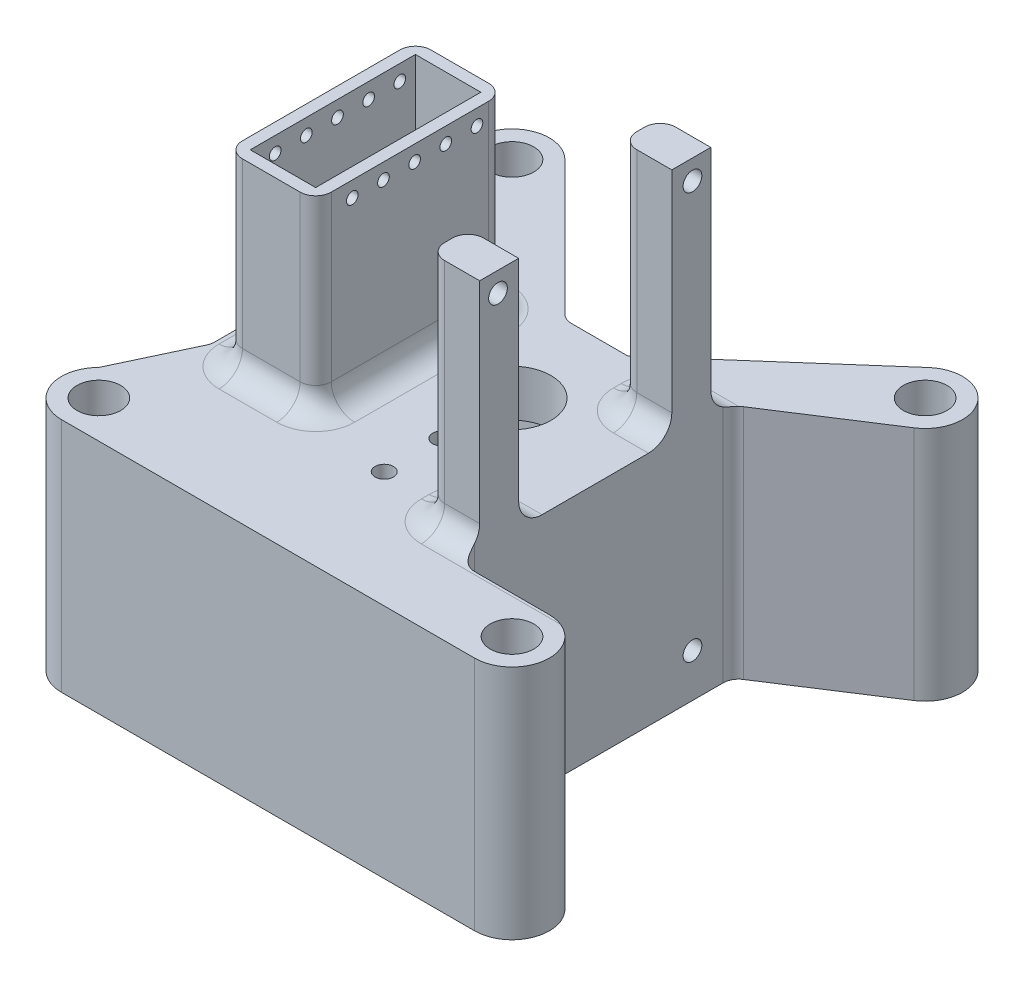
SolidWorks part; units mm, degrees
ref_plane "Front Plane" through (0, 0, 0) normal (0, 0, 1) x (1, 0, 0)
ref_plane "Top Plane" through (0, 0, 0) normal (0, 1, 0) x (1, 0, 0)
ref_plane "Right Plane" through (0, 0, 0) normal (1, 0, 0) x (0, 0, -1)
sketch "Sketch3" plane through (0, 0, 0) normal (0, 1, 0) x (1, 0, 0)
  line L0 (-33.676, -39.772) -> (33.676, -39.772)
  line L1 (-33.676, -33.676) -> (33.676, -33.676) construction
  line L2 (-33.676, -33.676) -> (-33.676, 33.676) construction
  line L3 (-33.676, 33.676) -> (33.676, 33.676) construction
  line L4 (33.676, -33.676) -> (33.676, 33.676) construction
  line L5 (-33.676, -33.676) -> (33.676, 33.676) construction
  line L6 (-33.676, 33.676) -> (33.676, -33.676) construction
  line L7 (10.033, -30.099) -> (-10.033, -30.099)
  line L8 (10.033, -30.099) -> (10.033, 10.033)
  line L9 (10.033, 10.033) -> (3.556, 10.033)
  line L10 (-10.033, -30.099) -> (-10.033, 10.033)
  line L11 (10.033, -30.099) -> (-10.033, 10.033) construction
  line L12 (10.033, 10.033) -> (-10.033, -30.099) construction
  line L13 (33.676, -27.58) -> (18.923, -27.58)
  line L14 (-3.556, 15.367) -> (3.556, 15.367) construction
  line L15 (-3.556, 15.367) -> (-3.556, 10.033)
  line L16 (0, 10.033) -> (3.556, 10.033) construction
  line L17 (3.556, 15.367) -> (3.556, 10.033)
  line L18 (-3.556, 15.367) -> (3.556, 10.033) construction
  line L19 (-3.556, 10.033) -> (3.556, 15.367) construction
  line L20 (-25.781, 10.033) -> (-15.113, 10.033) construction
  line L21 (-25.781, 10.033) -> (-25.781, -16.891) construction
  line L22 (-25.781, -16.891) -> (-15.113, -16.891) construction
  line L23 (-15.113, 10.033) -> (-15.113, -16.891) construction
  line L24 (-25.781, 10.033) -> (-15.113, -16.891) construction
  line L25 (-25.781, -16.891) -> (-15.113, 10.033) construction
  line L26 (18.923, -27.58) -> (18.923, 16.87)
  line L27 (36.9874, 28.5578) -> (18.923, 16.87)
  line L28 (29.6563, 38.259) -> (3.556, 15.367)
  line L31 (0, 10.033) -> (-3.556, 10.033) construction
  line L32 (-29.3669, 37.9879) -> (-6.731, 15.367)
  line L33 (-6.731, 15.367) -> (-3.556, 15.367)
  line L34 (-3.556, 10.033) -> (-10.033, 10.033)
  line L35 (-3.556, 10.033) -> (0, 10.033) construction
  line L36 (3.556, 10.033) -> (0, 10.033) construction
  line L37 (-32.131, -16.891) -> (-32.131, 10.033)
  line L38 (34.003, -24.1637) -> (18.923, -24.1637) construction
  line L39 (34.003, -24.1637) -> (34.003, 13.4537) construction
  line L40 (34.003, 13.4537) -> (18.923, 13.4537) construction
  line L41 (18.923, -24.1637) -> (18.923, 13.4537) construction
  line L42 (34.003, -24.1637) -> (18.923, 13.4537) construction
  line L43 (34.003, 13.4537) -> (18.923, -24.1637) construction
  line L44 (-32.131, 10.033) -> (-39.4519, 31.7268)
  line L45 (-32.131, -16.891) -> (-37.9865, -29.3654)
  circle A0 centre (-33.676, 33.676) radius 3.556
  circle A1 centre (33.676, 33.676) radius 3.556
  circle A2 centre (33.676, -33.676) radius 3.556
  circle A3 centre (-33.676, -33.676) radius 3.556
  circle A4 centre (0, 0) radius 6.35 construction
  circle A5 centre (0, 0) radius 10.033 construction
  circle A6 centre (0, 0) radius 63.373 construction
  arc A7 (33.676, -39.772) -> (33.676, -27.58) centre (33.676, -33.676) ccw
  arc A8 (-39.772, -33.676) -> (-33.676, -39.772) centre (-33.676, -33.676) ccw
  arc A9 (-29.3669, 37.9879) -> (-39.772, 33.676) centre (-33.676, 33.676) ccw
  arc A10 (36.9874, 28.5578) -> (29.6563, 38.259) centre (33.676, 33.676) ccw
  arc A11 (27.58, 33.676) -> (29.3654, 29.3654) centre (33.676, 33.676) ccw construction
  arc A12 (29.6563, 38.259) -> (27.58, 33.676) centre (33.676, 33.676) ccw construction
  arc A13 (29.3654, 29.3654) -> (33.676, 27.58) centre (33.676, 33.676) ccw construction
  arc A14 (33.676, 27.58) -> (36.9874, 28.5578) centre (33.676, 33.676) ccw construction
  arc A15 (-27.58, 33.676) -> (-29.3669, 37.9879) centre (-33.676, 33.676) ccw construction
  arc A16 (-29.3654, 29.3654) -> (-27.58, 33.676) centre (-33.676, 33.676) ccw construction
  arc A17 (-33.676, 27.58) -> (-29.3654, 29.3654) centre (-33.676, 33.676) ccw construction
  arc A18 (-39.772, 33.676) -> (-39.4519, 31.7268) centre (-33.676, 33.676) ccw
  arc A19 (-37.9865, -29.3654) -> (-39.772, -33.676) centre (-33.676, -33.676) ccw
  arc A20 (-29.3654, -29.3654) -> (-33.676, -27.58) centre (-33.676, -33.676) ccw construction
  arc A21 (-27.58, -33.676) -> (-29.3654, -29.3654) centre (-33.676, -33.676) ccw construction
  arc A22 (-33.676, -39.772) -> (-27.58, -33.676) centre (-33.676, -33.676) ccw construction
  arc A23 (33.676, -27.58) -> (29.3654, -29.3654) centre (33.676, -33.676) ccw construction
  arc A24 (29.3654, -29.3654) -> (27.58, -33.676) centre (33.676, -33.676) ccw construction
  arc A25 (27.58, -33.676) -> (33.676, -39.772) centre (33.676, -33.676) ccw construction
  arc A26 (-39.4519, 31.7268) -> (-33.676, 27.58) centre (-33.676, 33.676) ccw construction
  arc A27 (-33.676, -27.58) -> (-37.9865, -29.3654) centre (-33.676, -33.676) ccw construction
  point P0 (0, 0)
  point P10 (0, -10.033)
  point P25 (0, 12.7)
  point P30 (3.556, 12.7)
  point P32 (-20.447, -3.429)
  point P53 (18.923, -5.355)
  point P55 (26.463, -5.355)
  point P64 (-32.131, -3.429)
  dimension "D2" = 7.112
  dimension "D5" = 12.7
  dimension "D6" = 126.746
  dimension "D1" = 95.25
  dimension "D3" = 40.132
  dimension "D4" = 20.066
  dimension "D7" = 2.54
  dimension "D8" = 5.334
  dimension "D9" = 7.112
  dimension "D10" = 10.668
  dimension "D11" = 26.924
  dimension "D12" = 5.08
  dimension "D13" = 8.89
  dimension "D14" = 171.65
  dimension "D15" = 352.506
  dimension "D16" = 44.45
  dimension "D17" = 37.6174
  dimension "D18" = 3.175
  dimension "D19" = 30.16
  dimension "D21" = 6.35
  dimension "D20" = 67.3519
extrude "Boss-Extrude1" add sketch "Sketch3" along normal blind 21.463
sketch "Sketch4" plane through (0, 21.463, 0) normal (0, 1, 0) x (1, 0, 0)
  line L0 (-3.556, 15.367) -> (3.556, 15.367) construction
  line L1 (-3.556, 10.033) -> (3.556, 10.033) construction
  line L2 (3.556, 15.367) -> (-3.556, 15.367)
  line L3 (-3.556, 10.033) -> (3.556, 10.033)
  line L16 (-10.033, 10.033) -> (-3.556, 10.033)
  line L17 (-3.556, 10.033) -> (-3.556, 15.367)
  line L18 (-3.556, 15.367) -> (-6.731, 15.367)
  line L19 (-6.731, 15.367) -> (-29.3669, 37.9879)
  line L20 (-39.4519, 31.7268) -> (-32.131, 10.033)
  line L21 (-33.676, -39.772) -> (33.676, -39.772)
  line L22 (33.676, -27.58) -> (18.923, -27.58)
  line L23 (18.923, -27.58) -> (18.923, 16.87)
  line L24 (18.923, 16.87) -> (36.9874, 28.5578)
  line L25 (29.6563, 38.259) -> (3.556, 15.367)
  line L27 (3.556, 15.367) -> (3.556, 10.033)
  line L28 (3.556, 10.033) -> (10.033, 10.033)
  line L29 (10.033, 10.033) -> (10.033, -30.099)
  line L30 (10.033, -30.099) -> (-10.033, -30.099)
  line L31 (-10.033, -30.099) -> (-10.033, 10.033)
  line L32 (-10.033, 10.033) -> (-3.556, 10.033)
  line L33 (-3.556, 10.033) -> (-3.556, 15.367) construction
  line L34 (-3.556, 15.367) -> (-6.731, 15.367)
  line L35 (-6.731, 15.367) -> (-29.3669, 37.9879)
  line L37 (-33.676, -39.772) -> (33.676, -39.772)
  line L38 (33.676, -27.58) -> (18.923, -27.58)
  line L39 (18.923, -27.58) -> (18.923, 16.87)
  line L40 (18.923, 16.87) -> (36.9874, 28.5578)
  line L41 (29.6563, 38.259) -> (3.556, 15.367)
  line L43 (3.556, 15.367) -> (3.556, 10.033) construction
  line L44 (3.556, 10.033) -> (10.033, 10.033)
  line L45 (10.033, 10.033) -> (10.033, -30.099)
  line L46 (10.033, -30.099) -> (-10.033, -30.099)
  line L47 (-10.033, -30.099) -> (-10.033, 10.033)
  line L52 (-39.4519, 31.7268) -> (-32.131, 10.033)
  line L53 (-32.131, 10.033) -> (-32.131, -16.891)
  line L54 (-32.131, 10.033) -> (-32.131, -16.891)
  line L55 (-32.131, -16.891) -> (-37.9865, -29.3654)
  line L56 (-32.131, -16.891) -> (-37.9865, -29.3654)
  circle A3 centre (33.676, -33.676) radius 3.556 construction
  arc A4 (-29.3669, 37.9879) -> (-39.4519, 31.7268) centre (-33.676, 33.676) ccw
  arc A5 (-37.9865, -29.3654) -> (-33.676, -39.772) centre (-33.676, -33.676) ccw
  arc A6 (33.676, -39.772) -> (33.676, -27.58) centre (33.676, -33.676) ccw
  arc A7 (36.9874, 28.5578) -> (29.6563, 38.259) centre (33.676, 33.676) ccw
  arc A8 (-29.3669, 37.9879) -> (-39.4519, 31.7268) centre (-33.676, 33.676) ccw
  arc A9 (-37.9865, -29.3654) -> (-33.676, -39.772) centre (-33.676, -33.676) ccw
  arc A10 (33.676, -39.772) -> (33.676, -27.58) centre (33.676, -33.676) ccw
  arc A11 (36.9874, 28.5578) -> (29.6563, 38.259) centre (33.676, 33.676) ccw
  circle A12 centre (33.676, -33.676) radius 3.556
  circle A13 centre (33.676, 33.676) radius 3.556 construction
  circle A14 centre (33.676, 33.676) radius 3.556
  circle A15 centre (-33.676, 33.676) radius 3.556 construction
  circle A16 centre (-33.676, 33.676) radius 3.556
  circle A17 centre (-33.676, -33.676) radius 3.556 construction
  circle A18 centre (-33.676, -33.676) radius 3.556
  dimension "D1" = 0
extrude "Boss-Extrude2" add sketch "Sketch4" along normal blind 7.366
sketch "Sketch5" plane through (0, 28.829, 0) normal (0, 1, 0) x (1, 0, 0)
  line L8 (3.556, 15.367) -> (-6.731, 15.367)
  line L9 (-6.731, 15.367) -> (-29.3669, 37.9879)
  line L10 (-39.4519, 31.7268) -> (-32.131, 10.033)
  line L11 (-33.676, -39.772) -> (33.676, -39.772)
  line L12 (33.676, -27.58) -> (18.923, -27.58)
  line L13 (18.923, -27.58) -> (18.923, 16.87)
  line L14 (18.923, 16.87) -> (36.9874, 28.5578)
  line L15 (29.6563, 38.259) -> (3.556, 15.367)
  line L16 (3.556, 15.367) -> (-6.731, 15.367)
  line L17 (-6.731, 15.367) -> (-29.3669, 37.9879)
  line L19 (-33.676, -39.772) -> (33.676, -39.772)
  line L20 (33.676, -27.58) -> (18.923, -27.58)
  line L21 (18.923, -27.58) -> (18.923, 16.87)
  line L22 (18.923, 16.87) -> (36.9874, 28.5578)
  line L23 (29.6563, 38.259) -> (3.556, 15.367)
  line L26 (-39.4519, 31.7268) -> (-32.131, 10.033)
  line L27 (-32.131, 10.033) -> (-32.131, -16.891)
  line L28 (-32.131, 10.033) -> (-32.131, -16.891)
  line L29 (-32.131, -16.891) -> (-37.9865, -29.3654)
  line L30 (-32.131, -16.891) -> (-37.9865, -29.3654)
  circle A0 centre (0, 0) radius 6.35 construction
  circle A1 centre (33.676, 33.676) radius 3.556
  circle A2 centre (33.676, 33.676) radius 3.556
  circle A3 centre (-33.676, 33.676) radius 3.556
  circle A4 centre (-33.676, 33.676) radius 3.556
  circle A5 centre (-33.676, -33.676) radius 3.556
  circle A6 centre (-33.676, -33.676) radius 3.556
  circle A7 centre (33.676, -33.676) radius 3.556
  circle A8 centre (33.676, -33.676) radius 3.556
  circle A9 centre (0, 0) radius 6.35
  arc A12 (-29.3669, 37.9879) -> (-39.4519, 31.7268) centre (-33.676, 33.676) ccw
  arc A13 (-37.9865, -29.3654) -> (-33.676, -39.772) centre (-33.676, -33.676) ccw
  arc A14 (33.676, -39.772) -> (33.676, -27.58) centre (33.676, -33.676) ccw
  arc A15 (36.9874, 28.5578) -> (29.6563, 38.259) centre (33.676, 33.676) ccw
  arc A16 (-29.3669, 37.9879) -> (-39.4519, 31.7268) centre (-33.676, 33.676) ccw
  arc A17 (-37.9865, -29.3654) -> (-33.676, -39.772) centre (-33.676, -33.676) ccw
  arc A18 (33.676, -39.772) -> (33.676, -27.58) centre (33.676, -33.676) ccw
  arc A19 (36.9874, 28.5578) -> (29.6563, 38.259) centre (33.676, 33.676) ccw
  dimension "D1" = 0
  dimension "D2" = 0
  dimension "D3" = 0
  dimension "D4" = 0
  dimension "D5" = 0
extrude "Boss-Extrude3" add sketch "Sketch5" along normal blind 7.62
sketch "Sketch6" plane through (0, 36.449, 0) normal (0, 1, 0) x (1, 0, 0)
  line L0 (-25.781, 10.033) -> (-25.781, -16.891) construction
  line L1 (-25.781, -16.891) -> (-15.113, -16.891) construction
  line L2 (-15.113, 10.033) -> (-15.113, -16.891) construction
  line L3 (-25.781, 10.033) -> (-15.113, 10.033) construction
  line L4 (-25.781, 10.033) -> (-25.781, -16.891) construction
  line L5 (-25.781, -16.891) -> (-15.113, -16.891) construction
  line L6 (-15.113, 10.033) -> (-15.113, -16.891) construction
  line L7 (-25.781, 10.033) -> (-15.113, 10.033) construction
  line L9 (-13.208, 11.938) -> (-27.686, 11.938)
  line L10 (-13.208, 11.938) -> (-13.208, -18.796)
  line L11 (-13.208, -18.796) -> (-27.686, -18.796)
  line L12 (-27.686, 11.938) -> (-27.686, -18.796)
  line L13 (-13.208, 11.938) -> (-27.686, -18.796) construction
  line L14 (-13.208, -18.796) -> (-27.686, 11.938) construction
  point P4 (-20.447, -3.429)
  point P11 (-20.447, -16.891)
  dimension "D1" = 1.905
  dimension "D2" = 1.905
extrude "Boss-Extrude4" add sketch "Sketch6" along normal blind 30.59
sketch "Sketch7" plane through (0, 67.039, 0) normal (0, 1, 0) x (1, 0, 0)
  line L0 (-25.781, 10.033) -> (-25.781, -16.891) construction
  line L1 (-25.781, -16.891) -> (-15.113, -16.891) construction
  line L2 (-15.113, 10.033) -> (-15.113, -16.891) construction
  line L3 (-25.781, 10.033) -> (-15.113, 10.033) construction
  line L4 (-25.781, 10.033) -> (-25.781, -16.891)
  line L5 (-25.781, -16.891) -> (-15.113, -16.891)
  line L6 (-15.113, 10.033) -> (-15.113, -16.891)
  line L7 (-25.781, 10.033) -> (-15.113, 10.033)
extrude "Cut-Extrude1" cut sketch "Sketch7" against normal blind 50.8
sketch "Sketch8" plane through (-27.686, 0, 0) normal (-1, 0, 0) x (0, 0, 1)
  line L0 (16.891, 16.239) -> (16.891, 67.039) construction
  line L1 (-10.033, 16.239) -> (-10.033, 67.039) construction
  line L2 (16.891, 16.239) -> (16.891, 67.039) construction
  line L3 (-10.033, 16.239) -> (-10.033, 67.039) construction
  line L4 (-7.493, 64.499) -> (-2.413, 64.499) construction
  circle A0 centre (-7.493, 64.499) radius 0.9525
  circle A1 centre (-2.413, 64.499) radius 0.9525
  circle A2 centre (2.667, 64.499) radius 0.9525
  circle A3 centre (7.747, 64.499) radius 0.9525
  circle A4 centre (12.827, 64.499) radius 0.9525
  dimension "D1" = 1.905
  dimension "D5" = 5.08
  dimension "D2" = 2.54
  dimension "D3" = 2.54
  dimension "D4" = 5
extrude "Cut-Extrude2" cut sketch "Sketch8" against normal through all
sketch "Sketch10" plane through (0, 36.449, 0) normal (0, 1, 0) x (1, 0, 0)
  line L0 (18.923, -27.58) -> (18.923, 16.87) construction
  line L1 (10.668, -24.19) -> (18.923, -24.19)
  line L2 (10.668, -24.19) -> (10.668, -17.84)
  line L3 (10.668, 13.48) -> (18.923, 13.48)
  line L4 (18.923, -24.19) -> (18.923, -17.84)
  line L5 (10.668, -24.19) -> (18.923, 13.48) construction
  line L6 (10.668, 13.48) -> (18.923, -24.19) construction
  line L7 (18.923, -27.58) -> (18.923, 16.87) construction
  line L8 (18.923, -17.84) -> (18.923, 7.13) construction
  line L9 (18.923, -17.84) -> (10.668, -17.84)
  line L10 (18.923, -17.84) -> (18.923, 7.13) construction
  line L11 (18.923, 7.13) -> (10.668, 7.13)
  line L12 (10.668, -17.84) -> (10.668, 7.13) construction
  line L13 (18.923, -17.84) -> (10.668, 7.13) construction
  line L14 (18.923, 7.13) -> (10.668, -17.84) construction
  line L15 (18.923, 7.13) -> (18.923, 13.48)
  line L16 (10.668, -17.84) -> (10.668, 7.13) construction
  line L17 (10.668, 7.13) -> (10.668, 13.48)
  point P0 (14.7955, -5.355)
  point P7 (18.923, -5.355)
  point P9 (14.7955, -5.355)
  dimension "D1" = 37.67
  dimension "D2" = 8.255
  dimension "D3" = 6.35
extrude "Boss-Extrude5" add sketch "Sketch10" along normal blind 38.1
sketch "Sketch9" plane through (18.923, 0, 0) normal (1, 0, 0) x (0, 0, -1)
  line L0 (-27.58, 0) -> (16.87, 0) construction
  line L1 (-21.205, 71.3) -> (10.495, 71.3) construction
  line L2 (-21.205, 71.3) -> (-21.205, 5) construction
  line L3 (-21.205, 5) -> (10.495, 5) construction
  line L4 (10.495, 71.3) -> (10.495, 5) construction
  line L5 (-21.205, 71.3) -> (10.495, 5) construction
  line L6 (-21.205, 5) -> (10.495, 71.3) construction
  circle A0 centre (-21.205, 71.3) radius 1.524
  circle A1 centre (10.495, 71.3) radius 1.524
  circle A2 centre (10.495, 5) radius 1.524
  circle A3 centre (-21.205, 5) radius 1.524
  point P0 (-5.355, 38.15)
  dimension "D4" = 3.048
  dimension "D1" = 31.7
  dimension "D2" = 66.3
  dimension "D3" = 5
extrude "Cut-Extrude3" cut sketch "Sketch9" against normal blind 5.75
sketch "Sketch13" plane through (0, 36.449, 0) normal (0, 1, 0) x (1, 0, 0)
  line L0 (0, -11.43) -> (0, -20.828) construction
  circle A0 centre (0, -11.43) radius 1.5
  circle A1 centre (0, -20.828) radius 1.5
  dimension "D2" = 3
  dimension "D1" = 9.398
  dimension "D3" = 11.43
extrude "Cut-Extrude4" cut sketch "Sketch13" against normal blind 4
fillet "Fillet1" radius 2.54 13 edges at (10.668, 55.499, 17.84) (10.668, 55.499, 24.19) (10.668, 55.499, -7.13) (10.668, 55.499, -13.48) (-27.686, 51.744, -11.938) (-13.208, 51.744, -11.938) (-13.208, 51.744, 18.796) (-27.686, 51.744, 18.796) (-32.131, 18.2245, 16.891) (-32.131, 18.2245, -10.033) (-6.731, 18.2245, -15.367) (18.923, 18.2245, -16.87) (18.923, 18.2245, 27.58)
fillet "Fillet2" radius 3.81 18 edges at (-13.9519, 36.449, -11.1941) (-13.208, 36.449, 3.429) (-13.9519, 36.449, 18.0521) (-20.447, 36.449, 18.796) (-26.9421, 36.449, 18.0521) (-27.686, 36.449, 3.429) (-26.9421, 36.449, -11.1941) (16.0655, 36.449, 24.19) (11.4119, 36.449, 23.446) (10.668, 36.449, 21.015) (11.4119, 36.449, 18.5839) (16.0655, 36.449, -7.13) (11.4119, 36.449, -7.874) (10.668, 36.449, -10.305) (11.4119, 36.449, -12.7361) (-20.447, 36.449, -11.938) (16.0655, 36.449, 17.84) (16.0655, 36.449, -13.48)
sketch "Sketch14" plane through (0, 0, 0) normal (0, -1, 0) x (1, 0, 0)
  line L17 (-3.556, -10.033) -> (-10.033, -10.033)
  line L18 (-10.033, -10.033) -> (-10.033, 30.099)
  line L19 (-10.033, 30.099) -> (10.033, 30.099)
  line L20 (10.033, 30.099) -> (10.033, -10.033)
  line L21 (10.033, -10.033) -> (3.556, -10.033)
  line L22 (3.556, -10.033) -> (3.556, -15.367)
  line L23 (3.556, -15.367) -> (29.6563, -38.259)
  line L24 (36.9874, -28.5578) -> (20.0832, -17.6207)
  line L25 (18.923, -15.4881) -> (18.923, 25.04)
  line L26 (21.463, 27.58) -> (33.676, 27.58)
  line L27 (33.676, 39.772) -> (-33.676, 39.772)
  line L28 (-37.9865, 29.3654) -> (-32.3717, 17.4038)
  line L29 (-32.131, 16.3245) -> (-32.131, -9.616)
  line L30 (-32.2643, -10.4281) -> (-39.4519, -31.7268)
  line L31 (-29.3669, -37.9879) -> (-7.4748, -16.1104)
  line L32 (-5.6794, -15.367) -> (-3.556, -15.367)
  line L33 (-3.556, -15.367) -> (-3.556, -10.033)
  line L34 (-3.556, -10.033) -> (-10.033, -10.033)
  line L35 (-10.033, -10.033) -> (-10.033, 30.099)
  line L36 (-10.033, 30.099) -> (10.033, 30.099)
  line L37 (10.033, 30.099) -> (10.033, -10.033)
  line L38 (10.033, -10.033) -> (3.556, -10.033)
  line L39 (3.556, -10.033) -> (3.556, -15.367)
  line L40 (3.556, -15.367) -> (29.6563, -38.259)
  line L41 (36.9874, -28.5578) -> (20.0832, -17.6207)
  line L42 (18.923, -15.4881) -> (18.923, 25.04)
  line L43 (21.463, 27.58) -> (33.676, 27.58)
  line L44 (33.676, 39.772) -> (-33.676, 39.772)
  line L45 (-37.9865, 29.3654) -> (-32.3717, 17.4038)
  line L46 (-32.131, 16.3245) -> (-32.131, -9.616)
  line L47 (-32.2643, -10.4281) -> (-39.4519, -31.7268)
  line L48 (-29.3669, -37.9879) -> (-7.4748, -16.1104)
  line L49 (-5.6794, -15.367) -> (-3.556, -15.367)
  line L50 (-3.556, -15.367) -> (-3.556, -10.033)
  circle A0 centre (-33.676, -33.676) radius 3.556 construction
  circle A1 centre (-33.676, -33.676) radius 3.556
  circle A2 centre (-33.676, 33.676) radius 3.556 construction
  circle A3 centre (-33.676, 33.676) radius 3.556
  circle A4 centre (33.676, 33.676) radius 3.556 construction
  circle A5 centre (33.676, 33.676) radius 3.556
  circle A6 centre (33.676, -33.676) radius 3.556 construction
  circle A7 centre (33.676, -33.676) radius 3.556
  arc A9 (29.6563, -38.259) -> (36.9874, -28.5578) centre (33.676, -33.676) ccw
  arc A10 (18.923, -15.4881) -> (20.0832, -17.6207) centre (21.463, -15.4881) ccw
  arc A11 (21.463, 27.58) -> (18.923, 25.04) centre (21.463, 25.04) ccw
  arc A12 (33.676, 27.58) -> (33.676, 39.772) centre (33.676, 33.676) ccw
  arc A13 (-33.676, 39.772) -> (-37.9865, 29.3654) centre (-33.676, 33.676) ccw
  arc A14 (-32.131, 16.3245) -> (-32.3717, 17.4038) centre (-34.671, 16.3245) ccw
  arc A15 (-32.2643, -10.4281) -> (-32.131, -9.616) centre (-34.671, -9.616) ccw
  arc A16 (-39.4519, -31.7268) -> (-29.3669, -37.9879) centre (-33.676, -33.676) ccw
  arc A17 (-5.6794, -15.367) -> (-7.4748, -16.1104) centre (-5.6794, -17.907) ccw
  arc A18 (29.6563, -38.259) -> (36.9874, -28.5578) centre (33.676, -33.676) ccw
  arc A19 (18.923, -15.4881) -> (20.0832, -17.6207) centre (21.463, -15.4881) ccw
  arc A20 (21.463, 27.58) -> (18.923, 25.04) centre (21.463, 25.04) ccw
  arc A21 (33.676, 27.58) -> (33.676, 39.772) centre (33.676, 33.676) ccw
  arc A22 (-33.676, 39.772) -> (-37.9865, 29.3654) centre (-33.676, 33.676) ccw
  arc A23 (-32.131, 16.3245) -> (-32.3717, 17.4038) centre (-34.671, 16.3245) ccw
  arc A24 (-32.2643, -10.4281) -> (-32.131, -9.616) centre (-34.671, -9.616) ccw
  arc A25 (-39.4519, -31.7268) -> (-29.3669, -37.9879) centre (-33.676, -33.676) ccw
  arc A26 (-5.6794, -15.367) -> (-7.4748, -16.1104) centre (-5.6794, -17.907) ccw
  dimension "D1" = 0
extrude "Boss-Extrude6" add sketch "Sketch14" along normal blind 2.0585
equation "\"AIRFRAME_OD\"= 5.15in"
equation "\"AIRFRAME_ID\"= 4.99in"
equation "\"FLAT_T\"= 0.125in"
equation "\"COUPLER_OD\"= 4.998in"
equation "\"COUPLER_ID\"= 4.85in"
equation "\"NOSE_EXP_L\"= 27in"
equation "\"NOSE_SHOULDER_L\"= 5in"
equation "\"MAIN_L\"= 30in"
equation "\"RECO_COUP_L\"= 10in"
equation "\"RECO_SWITCH_L\"= 2in"
equation "\"RECO_ROD_X\"= 3.5in"
equation "\"DROGUE_L\"= 20in"
equation "\"ATS_FORE_COUP_L\"= 5.5in"
equation "\"ATS_AFT_COUP_L\"= 4.5in"
equation "\"ATS_ROD_X\"= 3.75in"
equation "\"LOWER_L\"= 30in"
equation "\"FIN_ROOT\"= 8in"
equation "\"FIN_X\"= 0.75in"
equation "\"FIN_N\"= 4"
equation "\"MOTOR_OD\"= 3.091in"
equation "\"MOTOR_ID\"= 3.00in"
equation "\"MOTOR_L\"= 14in"
equation "\"CR_AFT_X\"= 0.5in"
equation "\"CR_FORE_X\"= 9.25in"
equation "\"MOTOR_LOWER_X\"= 2in"
equation "\"D1@Sketch3\"=\"ATS_ROD_X\""
equation "\"D6@Sketch3\"=\"AIRFRAME_ID\""
